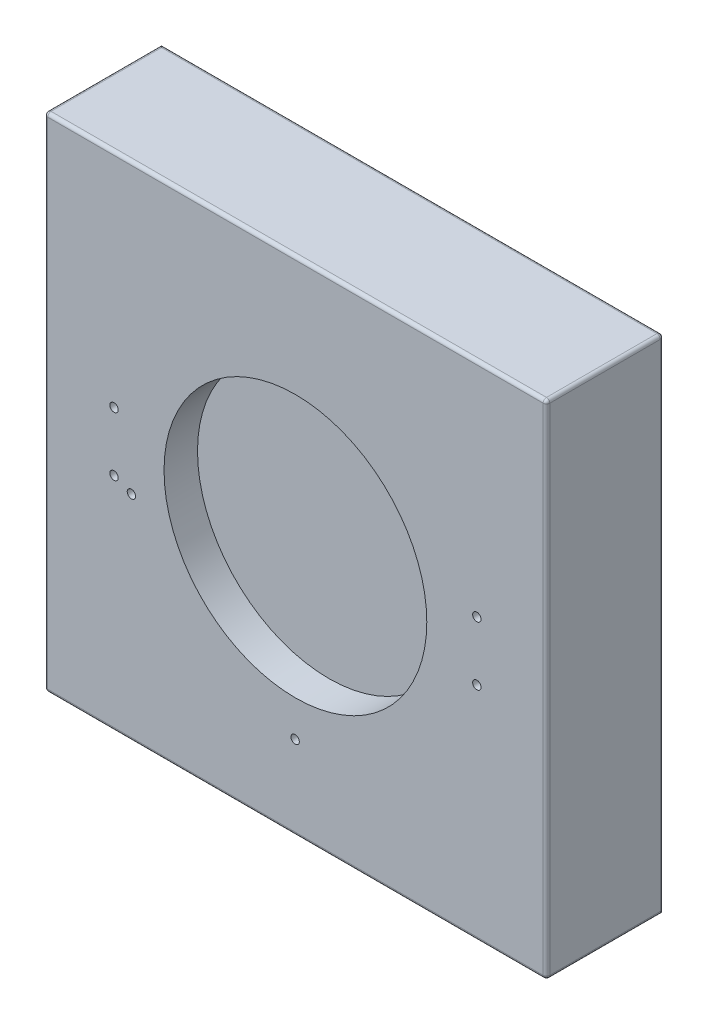
SolidWorks part; units mm, degrees
material "PLA"
ref_plane "Front Plane" through (0, 0, 0) normal (0, 0, 1) x (1, 0, 0)
ref_plane "Top Plane" through (0, 0, 0) normal (0, 1, 0) x (1, 0, 0)
ref_plane "Right Plane" through (0, 0, 0) normal (1, 0, 0) x (0, 0, -1)
sketch "Sketch1" plane through (0, 0, 0) normal (0, 0, 1) x (1, 0, 0)
  line L1 (-75, -75) -> (75, -75)
  line L2 (-75, -75) -> (-75, 75)
  line L3 (-75, 75) -> (75, 75)
  line L4 (75, -75) -> (75, 75)
  line L5 (-75, -75) -> (75, 75) construction
  line L6 (-75, 75) -> (75, -75) construction
  line L7 (-20.5, -25) -> (20.5, -25)
  line L8 (-20.5, -25) -> (-20.5, 25)
  line L9 (-20.5, 25) -> (20.5, 25)
  line L10 (20.5, -25) -> (20.5, 25)
  line L11 (-20.5, -25) -> (20.5, 25) construction
  line L12 (-20.5, 25) -> (20.5, -25) construction
  point P0 (0, 0)
  point P6 (0, 0)
  dimension "D1" = 150
  dimension "D2" = 150
extrude "Boss-Extrude1" add sketch "Sketch1" against normal blind 35 contours L2 L3 L4 L1
sketch "Sketch2" plane through (0, 0, 0) normal (0, 0, 1) x (1, 0, 0)
  circle A0 centre (0, 0) radius 39.25
  dimension "D1" = 78.5
fillet "Fillet1" radius 1 10 edges at (75, -75, -17.5) (-75, -75, -17.5) (-75, 75, -17.5) (75, 0, -35) (0, 75, -35) (75, 75, -17.5) (0, -75, 0) (-75, 0, 0) (75, 0, 0) (0, 75, 0)
sketch "Sketch7" plane through (0, 0, 0) normal (0, 1, 0) x (1, 0, 0)
  line L1 (-39.7685, 40.3246) -> (-29.7685, 40.3246)
  line L2 (-39.7685, 40.3246) -> (-39.7685, 30.3246)
  line L3 (-39.7685, 30.3246) -> (-29.7685, 30.3246)
  line L4 (-29.7685, 40.3246) -> (-29.7685, 30.3246)
  dimension "D1" = 10
  dimension "D2" = 10
ref_axis "Axis2" through (0, 0, 0) along (0, 0, -1)
extrude "Cut-Extrude4" cut sketch "Sketch2" against normal blind 10 contours A0
sketch "Sketch10" plane through (-75, 0, 0) normal (-1, 0, 0) x (0, 0, 1)
  line L0 (-35, 0) -> (0, 0) construction
  line L1 (-35, -74) -> (-35, 74) construction
sketch "Sketch19" plane through (0, 0, -35) normal (0, 0, -1) x (-1, 0, 0)
  line L0 (0.5, 74) -> (0, -75) construction
  line L1 (75, 74) -> (-74, 74) construction
  line L2 (74, -75) -> (-74, -75) construction
sketch "Sketch20" plane through (75, 0, 0) normal (1, 0, 0) x (0, 0, -1)
  line L0 (1, 0) -> (35, 0) construction
  line L1 (1, 74) -> (1, -74) construction
  line L2 (35, 0) -> (0, 0) construction
sketch "Sketch21" plane through (0, 0, 0) normal (0, 0, 1) x (1, 0, 0)
  circle A0 centre (54.1909, 8.8) radius 1.5
  circle A1 centre (54.1909, -8.8) radius 1.5
  circle A2 centre (-54.1909, 8.8) radius 1.5
  circle A3 centre (-54.1909, -8.8) radius 1.5
hole_wizard "Tap Drill for M3x0.5 Tap2" positions "Sketch22" profile "Sketch23" hole size "M3x0.5" standard "ANSI Metric" end condition through all
sketch "Sketch22" plane through (0, 0, 0) normal (0, 0, 1) x (1, 0, 0)
  point P0 (-54.1909, -8.8)
  point P3 (-54.1909, 8.8)
  point P6 (54.1909, -8.8)
  point P9 (54.1909, 8.8)
sketch "Sketch23" plane through (-54.1909, -8.8, 0) normal (1, 0, 0) x (0, -1, 0)
  line L0 (0, 0) -> (0, 35)
  line L1 (0, 35) -> (1.25, 35)
  line L2 (1.25, 35) -> (1.25, 0)
  line L5 (1.25, 0) -> (0, 0)
  line L11 (0, -6.35) -> (0, 107.95) construction
  dimension "Thru Hole Dia." = 2.5
  dimension "Thru Hole Depth" = 35
hole_wizard "Tap Drill for M3x0.5 Tap3" positions "Sketch25" profile "Sketch26" hole size "M3x0.5" standard "ANSI Metric" end condition through all
sketch "Sketch25" plane through (0, 0, 0) normal (0, 0, 1) x (1, 0, 0)
  line L0 (74, -75) -> (-74, -75) construction
  line L1 (-75, -74) -> (-75, 74) construction
  point P0 (-49, -11)
  dimension "D1" = 64
  dimension "D2" = 26
sketch "Sketch26" plane through (-49, -11, 0) normal (1, 0, 0) x (0, -1, 0)
  line L0 (0, 0) -> (0, 35)
  line L1 (0, 35) -> (1.25, 35)
  line L2 (1.25, 35) -> (1.25, 0)
  line L5 (1.25, 0) -> (0, 0)
  line L11 (0, -6.35) -> (0, 107.95) construction
  dimension "Thru Hole Dia." = 2.5
  dimension "Thru Hole Depth" = 35
hole_wizard "Tap Drill for M3x0.5 Tap5" positions "Sketch29" profile "Sketch30" hole size "M3x0.5" standard "ANSI Metric" end condition through all
sketch "Sketch29" plane through (0, 0, 0) normal (0, 0, 1) x (1, 0, 0)
  line L0 (-0.5, 74) -> (0, -75) construction
  circle A0 centre (-0.0839, -50) radius 3.4421
  point P0 (-0.0839, -50)
sketch "Sketch30" plane through (-0.0839, -50, 0) normal (1, 0, 0) x (0, -1, 0)
  line L0 (0, 0) -> (0, 35)
  line L1 (0, 35) -> (1.25, 35)
  line L2 (1.25, 35) -> (1.25, 0)
  line L5 (1.25, 0) -> (0, 0)
  line L11 (0, -6.35) -> (0, 107.95) construction
  dimension "Thru Hole Dia." = 2.5
  dimension "Thru Hole Depth" = 35
sketch "Sketch31" plane through (0, 0, -35) normal (0, 0, -1) x (-1, 0, 0)
  line L1 (-20.05, -25) -> (20.05, -25)
  line L2 (-20.05, -25) -> (-20.05, 25)
  line L3 (-20.05, 25) -> (20.05, 25)
  line L4 (20.05, -25) -> (20.05, 25)
  line L5 (-20.05, -25) -> (20.05, 25) construction
  line L6 (-20.05, 25) -> (20.05, -25) construction
  point P0 (0, 0)
extrude "Cut-Extrude5" cut sketch "Sketch31" against normal blind 20.3
